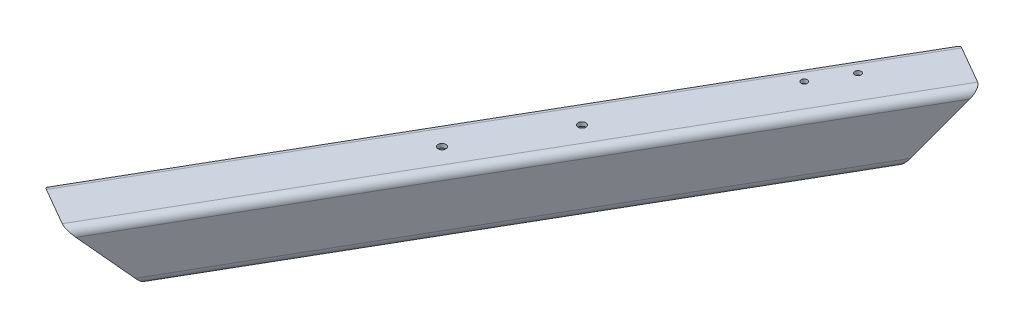
SolidWorks part; units mm, degrees
ref_plane "前视基准面" through (0, 0, 0) normal (0, 0, 1) x (1, 0, 0)
ref_plane "上视基准面" through (0, 0, 0) normal (0, 1, 0) x (1, 0, 0)
ref_plane "右视基准面" through (0, 0, 0) normal (1, 0, 0) x (0, 0, -1)
sketch "草图1" plane through (0, 0, 0) normal (0, 1, 0) x (1, 0, 0)
  line L0 (0, 0) -> (-39, 22.5167) construction
  line L1 (52, 0) -> (26, 45.0333) construction
  line L2 (26, 45.0333) -> (-26, 45.0333) construction
  line L3 (-26, 45.0333) -> (-52, 0) construction
  line L4 (-52, 0) -> (-26, -45.0333) construction
  line L5 (-26, -45.0333) -> (26, -45.0333) construction
  line L6 (26, -45.0333) -> (52, 0) construction
  line L7 (-39, 22.5167) -> (61, 195.7217)
  circle A0 centre (0, 0) radius 45.0333 construction
  dimension "D1" = 52
  dimension "D2" = 200
ref_plane "基准面1" through (-39, 0, -22.5167) normal (-0.5, 0, 0.866) x (0.866, 0, 0.5)
sketch "草图2" plane through (-39, 0, -22.5167) normal (-0.5, 0, 0.866) x (0.866, 0, 0.5)
  line L0 (-11, -13) -> (11, -13)
  line L1 (-11, -15) -> (11, -15)
  line L2 (-15, -11) -> (-15, 11)
  line L3 (-11, 15) -> (11, 15)
  line L4 (15, -11) -> (15, 11)
  line L5 (13, -11) -> (13, 11)
  line L6 (-11, 13) -> (11, 13)
  line L7 (-13, -11) -> (-13, 11)
  arc A0 (-11, -15) -> (-15, -11) centre (-11, -11) cw
  arc A1 (11, -15) -> (15, -11) centre (11, -11) ccw
  arc A2 (11, 15) -> (15, 11) centre (11, 11) cw
  arc A3 (-15, 11) -> (-11, 15) centre (-11, 11) cw
  arc A4 (11, -13) -> (13, -11) centre (11, -11) ccw
  arc A5 (11, 13) -> (13, 11) centre (11, 11) cw
  arc A6 (-13, 11) -> (-11, 13) centre (-11, 11) cw
  arc A7 (-11, -13) -> (-13, -11) centre (-11, -11) cw
sweep "扫描1" add profiles "草图2" path "草图1"
mirror "镜向1" about plane through (-39, 0, -22.5167) normal (-0.5, 0, 0.866) of "扫描1"
sketch "草图3" plane through (0, 0, 0) normal (0, 1, 0) x (1, 0, 0)
  circle A0 centre (-26, 45.0333) radius 2
  circle A1 centre (-52, 0) radius 2
  dimension "D1" = 4
extrude "切除-拉伸1" cut sketch "草图3" against normal through all both and the other way through all
sketch "草图5" plane through (-26.0096, 0, -15.0167) normal (0.866, 0, 0.5) x (0.5, 0, -0.866)
  line L0 (0, 15) -> (0, -59.6529) construction
  line L1 (-200, 15) -> (200, 15) construction
  line L2 (0, 28.6) -> (0, -28.6) construction
  line L3 (-200, -15) -> (-140, -15)
  line L4 (-200, -15) -> (200, -15) construction
  line L5 (-140, -15) -> (-170, 15)
  line L6 (-170, 15) -> (-200, 15)
  line L7 (-200, 15) -> (-200, -15)
  line L8 (200, 15) -> (200, -15)
  line L9 (170, 15) -> (200, 15)
  line L10 (140, -15) -> (170, 15)
  line L11 (200, -15) -> (140, -15)
  dimension "D1" = 60
  dimension "D2" = 30
extrude "切除-拉伸2" cut sketch "草图5" against normal through all
sketch "草图6" plane through (0, 15, 0) normal (0, 1, 0) x (1, 0, 0)
  line L0 (-124, -124.7077) -> (46, 169.741) construction
  line L1 (-133.5263, -119.2077) -> (-114.4737, -130.2077) construction
  line L2 (36.4737, 175.241) -> (55.5263, 164.241) construction
  line L4 (-25.8454, 14.9219) -> (-52.1835, 30.1282) construction
  line L5 (-63.7683, 36.8167) -> (-14.2317, 8.2167) construction
  line L6 (23.7274, 142.1037) -> (6.8877, 112.9366) construction
  line L7 (-134.9904, -113.7436) -> (31.0096, 173.7769) construction
  circle A0 centre (11.2628, 120.5145) radius 1.6
  circle A1 centre (21.2628, 137.835) radius 1.6
  point P18 (0, 0)
  point P19 (0, 0)
  point P20 (13.6873, 119.1147)
  point P21 (0, 0)
  dimension "D1" = 3.2
  dimension "D2" = 20
  dimension "D3" = 110
  dimension "D4" = 9.53
extrude "切除-拉伸3" cut sketch "草图6" against normal up to next
